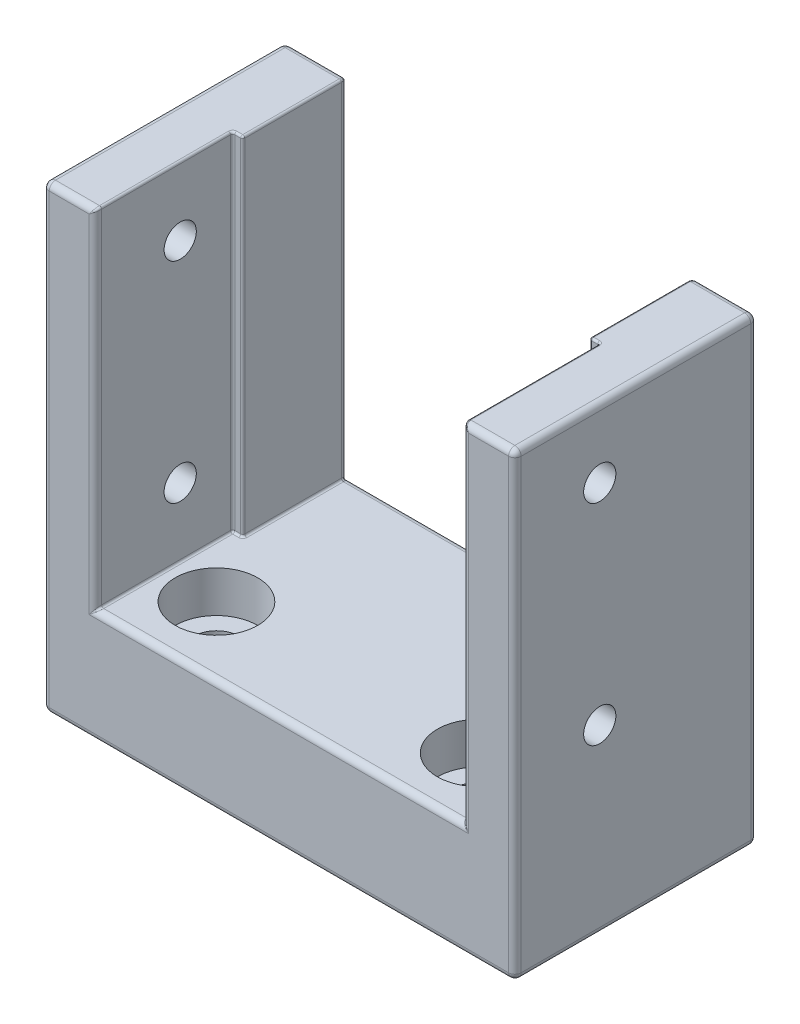
SolidWorks part; units mm, degrees
material "PLA"
ref_plane "Front Plane" through (0, 0, 0) normal (0, 0, 1) x (1, 0, 0)
ref_plane "Top Plane" through (0, 0, 0) normal (0, 1, 0) x (1, 0, 0)
ref_plane "Right Plane" through (0, 0, 0) normal (1, 0, 0) x (0, 0, -1)
sketch "Sketch1" plane through (0, 0, 0) normal (0, 1, 0) x (1, 0, 0)
  line L1 (-22.225, 14.6625) -> (22.225, 14.6625)
  line L2 (-22.225, 14.6625) -> (-22.225, -14.6625)
  line L3 (-22.225, -14.6625) -> (22.225, -14.6625)
  line L4 (22.225, 14.6625) -> (22.225, -14.6625)
  point P4 (0, -14.6625)
  point P6 (-22.225, 0)
  dimension "D1" = 29.325
  dimension "D2" = 44.45
extrude "Boss-Extrude1" add sketch "Sketch1" against normal blind 13.685
sketch "Sketch2" plane through (22.225, 0, 0) normal (1, 0, 0) x (0, 0, -1)
  line L0 (14.6625, -13.685) -> (14.6625, 0) construction
  line L1 (-14.6625, -13.685) -> (14.6625, -13.685)
  line L2 (-14.6625, -13.685) -> (-14.6625, 42)
  line L3 (-14.6625, 42) -> (14.6625, 42)
  line L4 (14.6625, -13.685) -> (14.6625, 42)
  point P5 (25.7459, -4.16)
  point P6 (25.7459, -29.56)
  dimension "D1" = 55.685
extrude "Boss-Extrude2" add sketch "Sketch2" along normal blind 6.35
hole_wizard "M3.5 Clearance Hole1" positions "Sketch5" profile "Sketch6" hole size "M3.5" standard "ANSI Metric" end condition through all
sketch "Sketch5" plane through (28.575, 0, 0) normal (1, 0, 0) x (0, 0, -1)
  line L1 (14.6625, 42) -> (-14.6625, 42) construction
  line L2 (-14.6625, 42) -> (-14.6625, -13.685) construction
  point P0 (-4.3875, 33.7)
  point P2 (-4.3875, 8.3)
  dimension "D1" = 10.275
  dimension "D2" = 8.3
  dimension "D3" = 25.4
sketch "Sketch6" plane through (28.575, 33.7, 4.3875) normal (0, 1, 0) x (0, 0, -1)
  line L0 (0, 0) -> (0, 50.8)
  line L1 (0, 50.8) -> (1.95, 50.8)
  line L2 (1.95, 50.8) -> (1.95, 0)
  line L5 (1.95, 0) -> (0, 0)
  line L11 (0, -6.35) -> (0, 107.95) construction
  dimension "Thru Hole Dia." = 3.9
  dimension "Thru Hole Depth" = 50.8
mirror "Mirror1" about plane through (0, 0, 0) normal (1, 0, 0) of "Boss-Extrude2", "M3.5 Clearance Hole1"
sketch "Sketch8" plane through (22.225, 0, 0) normal (-1, 0, 0) x (0, 0, 1)
  line L0 (-14.6625, 42) -> (14.6625, 42) construction
  line L1 (-14.6625, 0) -> (-1.9625, 0)
  line L2 (-14.6625, 0) -> (-14.6625, 42)
  line L3 (-14.6625, 42) -> (-1.9625, 42)
  line L4 (-1.9625, 0) -> (-1.9625, 42)
  dimension "D1" = 12.7
extrude "Boss-Extrude6" add sketch "Sketch8" along normal blind 1.225
mirror "Mirror2" about plane through (0, 0, 0) normal (1, 0, 0) of "Boss-Extrude6"
hole_wizard "CBORE for M5 SHCS1" positions "Sketch9" profile "Sketch10" counterbore size "M5" standard "ANSI Metric" end condition through all
sketch "Sketch9" plane through (0, 0, 0) normal (0, 1, 0) x (1, 0, 0)
  line L0 (-22.225, 1.9625) -> (-22.225, -14.6625) construction
  line L1 (0, -39.358) -> (0, 39.358) construction
  point P0 (15.875, -6.35)
  point P2 (-15.875, -6.35)
  point P8 (-22.225, -6.35)
  dimension "D1" = 15.875
  dimension "D2" = 15.875
sketch "Sketch10" plane through (15.875, 0, 6.35) normal (1, 0, 0) x (0, 0, 1)
  line L0 (0, 0) -> (0, 13.685)
  line L1 (0, 13.685) -> (2.75, 13.685)
  line L3 (2.75, 13.685) -> (2.75, 5)
  line L4 (2.75, 5) -> (5, 5)
  line L5 (5, 5) -> (5, 0)
  line L7 (5, 0) -> (0, 0)
  line L11 (0, -6.35) -> (0, 107.95) construction
  dimension "Thru Hole Dia." = 5.5
  dimension "Thru Hole Depth" = 13.685
  dimension "C'Bore Dia." = 10
  dimension "C'Bore Depth" = 5
fillet "Fillet1" radius 0.762 22 edges at (-21, 21, -14.6625) (-24.7875, 42, -14.6625) (-28.575, 14.1575, -14.6625) (28.575, 14.1575, -14.6625) (24.7875, 42, -14.6625) (21, 21, -14.6625) (0, 0, -14.6625) (22.225, 21, 14.6625) (25.4, 42, 14.6625) (28.575, 14.1575, 14.6625) (-28.575, 14.1575, 14.6625) (-25.4, 42, 14.6625) (-22.225, 21, 14.6625) (0, 0, 14.6625) (28.575, -13.685, 0) (0, -13.685, -14.6625) (-28.575, -13.685, 0) (0, -13.685, 14.6625) (-15.875, -13.685, 9.1) (15.875, -13.685, 9.1) (28.575, 42, 0) (-28.575, 42, 0)
fillet "Fillet2" radius 0.254 24 edges at (-21.2232, -0.2232, -14.4393) (21.2232, -0.2232, -14.4393) (22.4482, 41.7768, 14.4393) (-21, 0, -7.9315) (21, 0, -7.9315) (22.225, 42, 5.969) (-22.4482, -0.2232, 14.4393) (-21.2232, 41.7768, -14.4393) (-22.4482, 41.7768, 14.4393) (22.4482, -0.2232, 14.4393) (21.2232, 41.7768, -14.4393) (-22.225, 0, 5.969) (-21.6125, 0, -1.9625) (-21, 42, -7.9315) (-21, 21, -1.9625) (-22.225, 21, -1.9625) (-21.6125, 42, -1.9625) (-22.225, 42, 5.969) (21.6125, 0, -1.9625) (22.225, 0, 5.969) (21.6125, 42, -1.9625) (21, 21, -1.9625) (22.225, 21, -1.9625) (21, 42, -7.9315)
